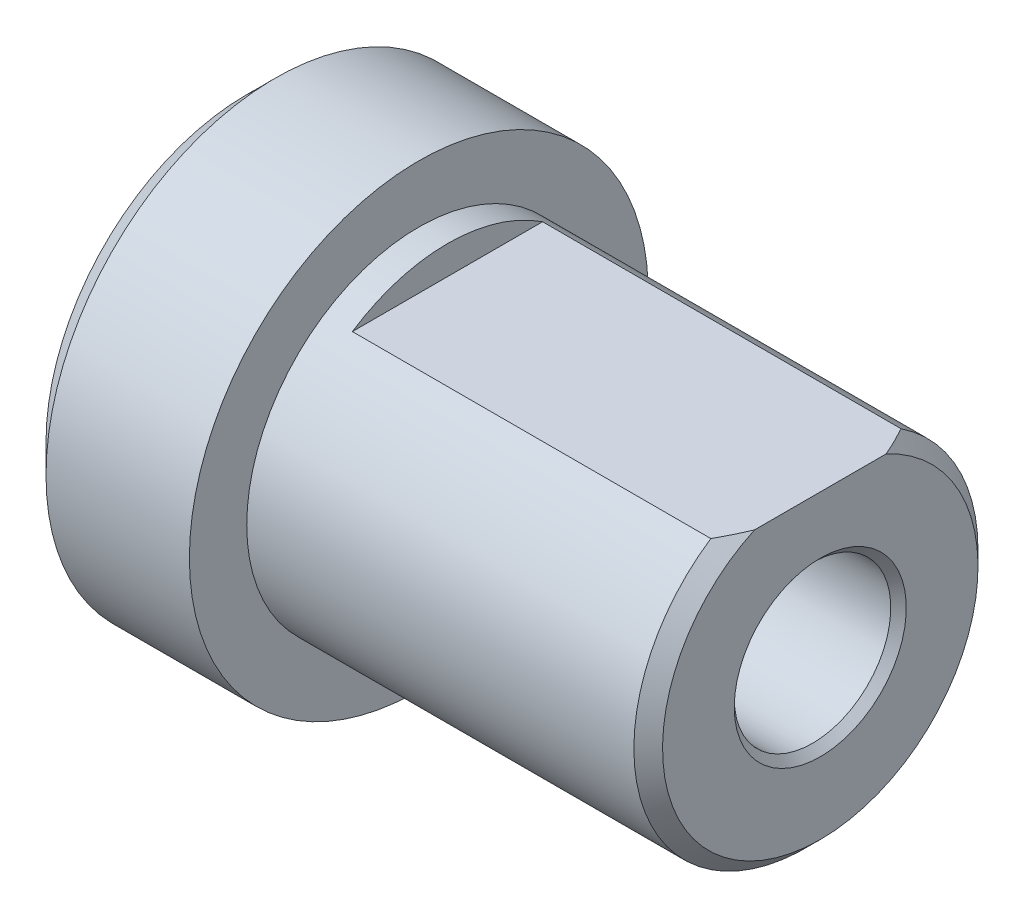
SolidWorks part; units mm, degrees
ref_plane "前视基准面" through (0, 0, 0) normal (0, 0, 1) x (1, 0, 0)
ref_plane "上视基准面" through (0, 0, 0) normal (0, 1, 0) x (1, 0, 0)
ref_plane "右视基准面" through (0, 0, 0) normal (1, 0, 0) x (0, 0, -1)
sketch "草图1" plane through (0, 0, 0) normal (0, 0, 1) x (1, 0, 0)
  line L0 (-10, 1.5) -> (-9.8645, 1.3645)
  line L1 (-9.8645, 1.3645) -> (-0.1355, 1.3645)
  line L2 (-0.1355, 1.3645) -> (0, 1.5)
  line L3 (0, 1.5) -> (0, 3)
  line L4 (0, 3) -> (-7, 3)
  line L5 (-7, 3) -> (-7, 4)
  line L6 (-7, 4) -> (-9.5, 4)
  line L7 (-9.5, 4) -> (-10, 3.5)
  line L8 (-10, 3.5) -> (-10, 1.5)
  line L9 (0, 0) -> (-10, 0) construction
revolve "旋转1" add sketch "草图1" angle 360 about L9 reverse direction yes
cosmetic thread "装饰螺纹线1"
ref_plane "基准面4" through (0, 2.5, 0) normal (0, 1, 0) x (1, 0, 0)
sketch "草图2" plane through (0, 2.5, 0) normal (0, 1, 0) x (1, 0, 0)
  line L0 (-6.5, 4) -> (-6.5, -4)
  line L1 (-6.5, -4) -> (0, -4)
  line L2 (0, -4) -> (0, 4)
  line L3 (0, 4) -> (-6.5, 4)
extrude "切除-拉伸1" cut sketch "草图2" along normal blind 3
ref_plane "基准面5" through (10, 0, 0) normal (1, 0, 0) x (0, 0, -1)
sketch "草图3" plane through (0, 0, 0) normal (0, 0, 1) x (1, 0, 0)
  line L0 (-0.25, 3) -> (0, 2.75)
  line L1 (0, 2.75) -> (0, 3)
  line L2 (0, 3) -> (-0.25, 3)
  line L3 (0, 0) -> (-0.25, 0) construction
revolve "切除-旋转1" cut sketch "草图3" angle 360 about L3 reverse direction yes
ref_plane "基准面6" through (2.5, 0, 0) normal (1, 0, 0) x (0, 0, -1)
ref_plane "基准面7" through (-2.5, 0, 0) normal (1, 0, 0) x (0, 0, -1)
ref_plane "基准面8" through (2, 0, 0) normal (1, 0, 0) x (0, 0, -1)
ref_plane "基准面9" through (0, 0, 4.3) normal (0, 0, 1) x (1, 0, 0)
ref_plane "mnnut_to_mnscrew XY" through (0, 0, 0) normal (1, 0, 0) x (0, 0, -1)
ref_plane "mnnut_to_mnscrew XZ" through (0, 0, 0) normal (0, -1, 0) x (-1, 0, 0)
ref_plane "mnnut_to_mnscrew YZ" through (0, 0, 0) normal (0, 0, -1) x (-1, 0, 0)
ref_axis "mnnut_to_mnscrew X" through (0, 0, 80.9) along (0, 0, -1)
ref_axis "mnnut_to_mnscrew Y" through (0, -50, 0) along (0, 1, 0)
ref_axis "mnnut_to_mnscrew Z" through (80.9, 0, 0) along (-1, 0, 0)
sketch3d "mnnut_to_mnscrew"
  point P0 (0, 0, 0)
ref_plane "rnut_to_rscrew XY" through (0, 0, 0) normal (-1, 0, 0) x (0, 0, 1)
ref_plane "rnut_to_rscrew XZ" through (0, 0, 0) normal (0, 1, 0) x (1, 0, 0)
ref_plane "rnut_to_rscrew YZ" through (0, 0, 0) normal (0, 0, -1) x (-1, 0, 0)
ref_axis "rnut_to_rscrew X" through (0, 0, 80.9) along (0, 0, -1)
ref_axis "rnut_to_rscrew Y" through (0, 50, 0) along (0, -1, 0)
ref_axis "rnut_to_rscrew Z" through (-80.9, 0, 0) along (1, 0, 0)
sketch3d "rnut_to_rscrew"
  point P0 (0, 0, 0)
ref_plane "rnut_to_rnut2 XY" through (2.5, 0, 0) normal (1, 0, 0) x (0, 0, -1)
ref_plane "rnut_to_rnut2 XZ" through (0, 0, 0) normal (0, -1, 0) x (-1, 0, 0)
ref_plane "rnut_to_rnut2 YZ" through (0, 0, 0) normal (0, 0, -1) x (-1, 0, 0)
ref_axis "rnut_to_rnut2 X" through (2.5, 0, 80.9) along (0, 0, -1)
ref_axis "rnut_to_rnut2 Y" through (2.5, -50, 0) along (0, 1, 0)
ref_axis "rnut_to_rnut2 Z" through (80.9, 0, 0) along (-1, 0, 0)
sketch3d "rnut_to_rnut2"
  point P0 (2.5, 0, 0)
ref_plane "2 XY" through (-2.5, 0, 0) normal (1, 0, 0) x (0, 0, -1)
ref_plane "2 XZ" through (0, 0, 0) normal (0, -1, 0) x (-1, 0, 0)
ref_plane "2 YZ" through (0, 0, 0) normal (0, 0, -1) x (-1, 0, 0)
ref_axis "2 X" through (-2.5, 0, 80.9) along (0, 0, -1)
ref_axis "2 Y" through (-2.5, -50, 0) along (0, 1, 0)
ref_axis "2 Z" through (80.9, 0, 0) along (-1, 0, 0)
sketch3d "2"
  point P0 (-2.5, 0, 0)
ref_plane "3 XY" through (2, 0, 0) normal (1, 0, 0) x (0, 0, -1)
ref_plane "3 XZ" through (0, 0, 0) normal (0, -1, 0) x (-1, 0, 0)
ref_plane "3 YZ" through (0, 0, 0) normal (0, 0, -1) x (-1, 0, 0)
ref_axis "3 X" through (2, 0, 80.9) along (0, 0, -1)
ref_axis "3 Y" through (2, -50, 0) along (0, 1, 0)
ref_axis "3 Z" through (80.9, 0, 0) along (-1, 0, 0)
sketch3d "3"
  point P0 (2, 0, 0)
ref_plane "to_clamp XY" through (0, 0, 4.3) normal (0, 0, 1) x (1, 0, 0)
ref_plane "to_clamp XZ" through (0, 0, 0) normal (0, -1, 0) x (-1, 0, 0)
ref_plane "to_clamp YZ" through (10, 0, 0) normal (1, 0, 0) x (0, 0, -1)
ref_axis "to_clamp X" through (-80.9, 0, 4.3) along (1, 0, 0)
ref_axis "to_clamp Y" through (10, -50, 4.3) along (0, 1, 0)
ref_axis "to_clamp Z" through (10, 0, 80.9) along (0, 0, -1)
sketch3d "to_clamp"
  point P0 (10, 0, 4.3)
